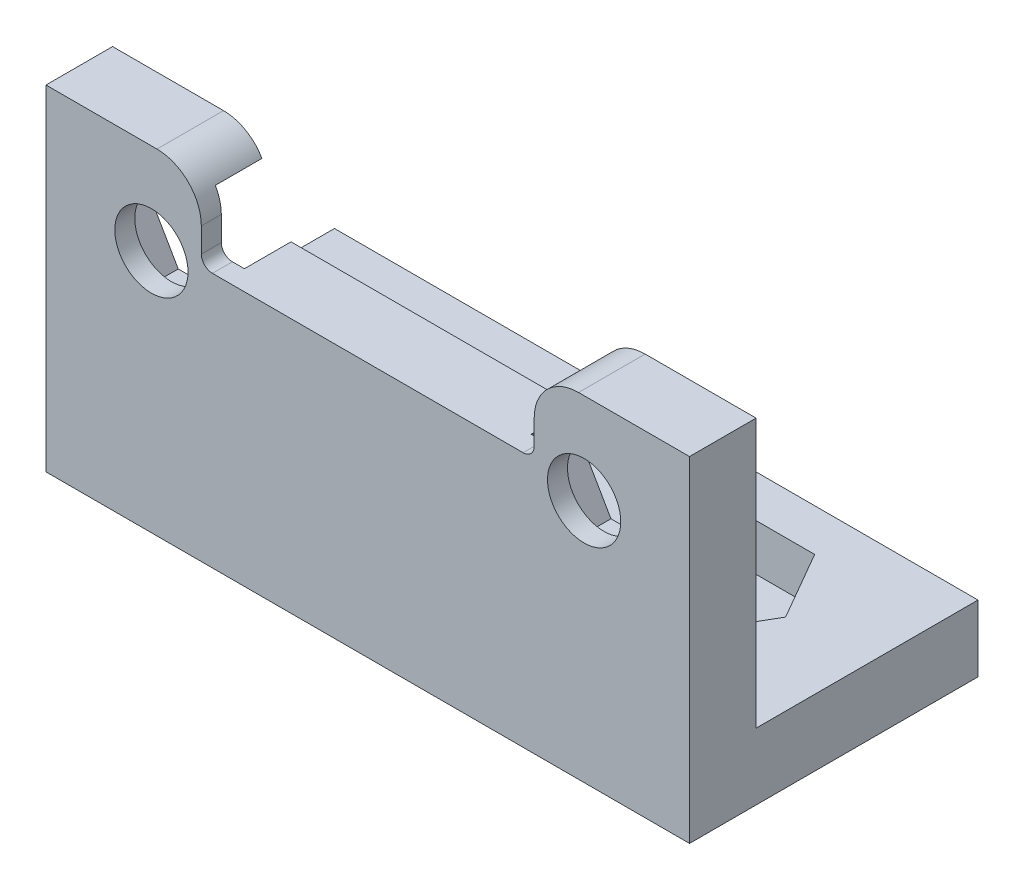
SolidWorks part; units mm, degrees
ref_plane "Front Plane" through (0, 0, 0) normal (0, 0, 1) x (1, 0, 0)
ref_plane "Top Plane" through (0, 0, 0) normal (0, 1, 0) x (1, 0, 0)
ref_plane "Right Plane" through (0, 0, 0) normal (1, 0, 0) x (0, 0, -1)
sketch "Sketch1" plane through (0, 0, 0) normal (0, 0, 1) x (1, 0, 0)
  line L0 (14.5, 8) -> (14.5, 0) construction
  line L1 (0, 0) -> (29, 0)
  line L2 (0, 0) -> (0, 8)
  line L3 (0, 8) -> (29, 8)
  line L4 (29, 0) -> (29, 8)
  line L5 (22.4602, 9.1) -> (26.0398, 9.1)
  line L6 (6.5398, 2.9) -> (8.3296, 6)
  line L7 (8.3296, 6) -> (6.5398, 9.1)
  line L8 (6.5398, 9.1) -> (2.9602, 9.1)
  line L9 (2.9602, 9.1) -> (1.1704, 6)
  line L10 (1.1704, 6) -> (2.9602, 2.9)
  line L11 (2.9602, 2.9) -> (6.5398, 2.9)
  line L12 (0, 8) -> (7, 8)
  line L13 (0, 8) -> (0, 10.1)
  line L14 (0, 10.1) -> (7, 10.1)
  line L15 (7, 8) -> (7, 10.1)
  line L16 (26.0398, 9.1) -> (27.8296, 6)
  line L17 (27.8296, 6) -> (26.0398, 2.9)
  line L18 (26.0398, 2.9) -> (22.4602, 2.9)
  line L19 (22.4602, 2.9) -> (20.6704, 6)
  line L20 (29, 8) -> (29, 10.1)
  line L21 (22, 8) -> (22, 10.1)
  line L22 (29, 10.1) -> (22, 10.1)
  line L23 (20.6704, 6) -> (22.4602, 9.1)
  line L24 (6.5398, 9.1) -> (7, 9.1)
  line L25 (29, 10.1) -> (22, 10.1)
  line L26 (29, 10.1) -> (29, 8)
  line L27 (29, 8) -> (22, 8)
  line L28 (22, 10.1) -> (22, 8)
  line L29 (7, 8) -> (22, 8)
  line L30 (7, 8) -> (7, 7)
  line L31 (7.5, 6.5) -> (21.5, 6.5)
  line L32 (22, 8) -> (22, 7)
  line L33 (22.4602, 9.1) -> (22, 9.1)
  circle A0 centre (4.75, 6) radius 1.65
  circle A1 centre (4.75, 6) radius 3.1 construction
  circle A2 centre (24.25, 6) radius 1.65
  arc A3 (7, 7) -> (7.5, 6.5) centre (7.5, 7) ccw
  arc A4 (21.5, 6.5) -> (22, 7) centre (21.5, 7) ccw
  point P19 (24.25, 6)
  dimension "D4" = 3.3
  dimension "D5" = 6.2
  dimension "D6" = 2
  dimension "D10" = 0.5
  dimension "D11" = 0.5
  dimension "D1" = 29
  dimension "D2" = 8
  dimension "D3" = 9.75
  dimension "D7" = 1
  dimension "D8" = 7
  dimension "D9" = 1.5
extrude "Boss-Extrude1" add sketch "Sketch1" along normal blind 3 contours L3 L32 L31 L30 L7 L6 L11 L10 L9 L2 L1 L4 L16 L17 L18 L19 L23 | L10 L11 L6 L7 L3 L9 A0 | L8 L9 L3 L7 | L3 L15 L14 L13 L9 L8 L7 | L3 L23 L5 L16 L20 L22 L21 | L23 L3 L16 L5 | L23 L19 L18 L17 L16 L3 A2 | L24 L7 L15 | L23 L33 L21 | L26 L25 L28 L27 region at (14.5, 2.9693, 0) region at (2.8626, 9.2984, 0) region at (26.1374, 9.2984, 0) region at (4.7367, 8.5248, 0) region at (4.6626, 7.9121, 0) region at (27.1761, 6.9561, 0) region at (24.2633, 8.5248, 0) region at (6.8466, 8.8343, 0) region at (22.1534, 8.8343, 0)
extrude "Cut-Extrude1" cut sketch "Sketch1<3>" along normal blind 2.1 contours L23 L19 L18 L17 L16 L3 A2 | L23 L3 L16 L5 | L10 L11 L6 L7 L3 L9 A0 | L8 L9 L3 L7 | L23 L33 L21 | L24 L7 L15 region at (4.7367, 8.5248, 0) region at (4.6626, 7.9121, 0) region at (27.1761, 6.9561, 0) region at (24.2633, 8.5248, 0) region at (6.8466, 8.8343, 0) region at (22.1534, 8.8343, 0)
sketch "Sketch1<3>" plane through (0, 0, 0) normal (0, 0, 1) x (1, 0, 0) same geometry as "Sketch1"
fillet "Fillet3" radius 2 2 edges at (7, 10.1, 1.5) (22, 10.1, 1.5)
sketch "Sketch2" plane through (0, 0, 3) normal (0, 0, 1) x (1, 0, 0)
  line L0 (29, 0) -> (29, 10.1) construction
  line L1 (0, 0) -> (29, 0)
  line L2 (0, 0) -> (0, -5)
  line L3 (0, -5) -> (29, -5)
  line L4 (29, 0) -> (29, -5)
  line L6 (0, -5) -> (29, -5)
  line L7 (0, -5) -> (0, -2)
  line L8 (0, -2) -> (29, -2)
  line L9 (29, -5) -> (29, -2)
  line M10 (0, 0) -> (29, 0)
  dimension "D1" = 5
  dimension "D2" = 3
extrude "Boss-Extrude2" add sketch "Sketch2" against normal blind 3 contours L2 L8 L4 M10 region at (14.5, -1, 3)
extrude "Boss-Extrude3" add sketch "Sketch2<3>" against normal blind 13 contours L8 L2 L3 L4 region at (14.5, -3.5, 3)
sketch "Sketch2<3>" plane through (0, 0, 3) normal (0, 0, 1) x (1, 0, 0) same geometry as "Sketch2"
sketch "Sketch3" plane through (0, -2, 0) normal (0, 1, 0) x (1, 0, 0)
  line L0 (29, 5) -> (0, 5) construction
  line L1 (29, 10) -> (29, 0) construction
  line L2 (0, 10) -> (0, 0) construction
  line L3 (29, 5) -> (21.75, 5)
  line L4 (21.75, 5) -> (14.5, 5)
  line L5 (14.5, 5) -> (7.25, 5)
  line L6 (7.25, 5) -> (0, 5)
  line L7 (0, 10) -> (29, 10) construction
  line L8 (19.9602, 8.1) -> (18.1704, 5)
  line L9 (18.1704, 5) -> (19.9602, 1.9)
  line L10 (19.9602, 1.9) -> (23.5398, 1.9)
  line L11 (23.5398, 1.9) -> (25.3296, 5)
  line L12 (25.3296, 5) -> (23.5398, 8.1)
  line L13 (23.5398, 8.1) -> (19.9602, 8.1)
  line L14 (5.4602, 8.1) -> (3.6704, 5)
  line L15 (3.6704, 5) -> (5.4602, 1.9)
  line L16 (5.4602, 1.9) -> (9.0398, 1.9)
  line L17 (9.0398, 1.9) -> (10.8296, 5)
  line L18 (10.8296, 5) -> (9.0398, 8.1)
  line L19 (9.0398, 8.1) -> (5.4602, 8.1)
  circle A0 centre (21.75, 5) radius 1.6
  circle A1 centre (7.25, 5) radius 1.6
  circle A2 centre (21.75, 5) radius 3.1 construction
  circle A3 centre (7.25, 5) radius 3.1 construction
  point P6 (21.75, 5)
  point P7 (7.25, 5)
  dimension "D1" = 6.2
  dimension "D2" = 3.2
  dimension "D3" = 3.2
  dimension "D4" = 6.2
extrude "Cut-Extrude2" cut sketch "Sketch3" against normal through all contours L4 A0 L3 | L3 A0 L4 | L6 A1 L5 | L5 A1 L6 region at (21.75, -2, -4.3209) region at (21.75, -2, -5.6791) region at (7.25, -2, -4.3209) region at (7.25, -2, -5.6791)
extrude "Cut-Extrude3" cut sketch "Sketch3<3>" against normal blind 2.1 contours A0 L4 L9 L10 L11 L3 | A0 L3 L12 L13 L8 L4 | A1 L6 L15 L16 L17 L5 | A1 L5 L18 L19 L14 L6 region at (21.75, -2, -3.3996) region at (7.25, -2, -3.3996) region at (7.25, -2, -6.6004) region at (21.75, -2, -6.6004)
sketch "Sketch3<3>" plane through (0, -2, 0) normal (0, 1, 0) x (1, 0, 0) same geometry as "Sketch3"
